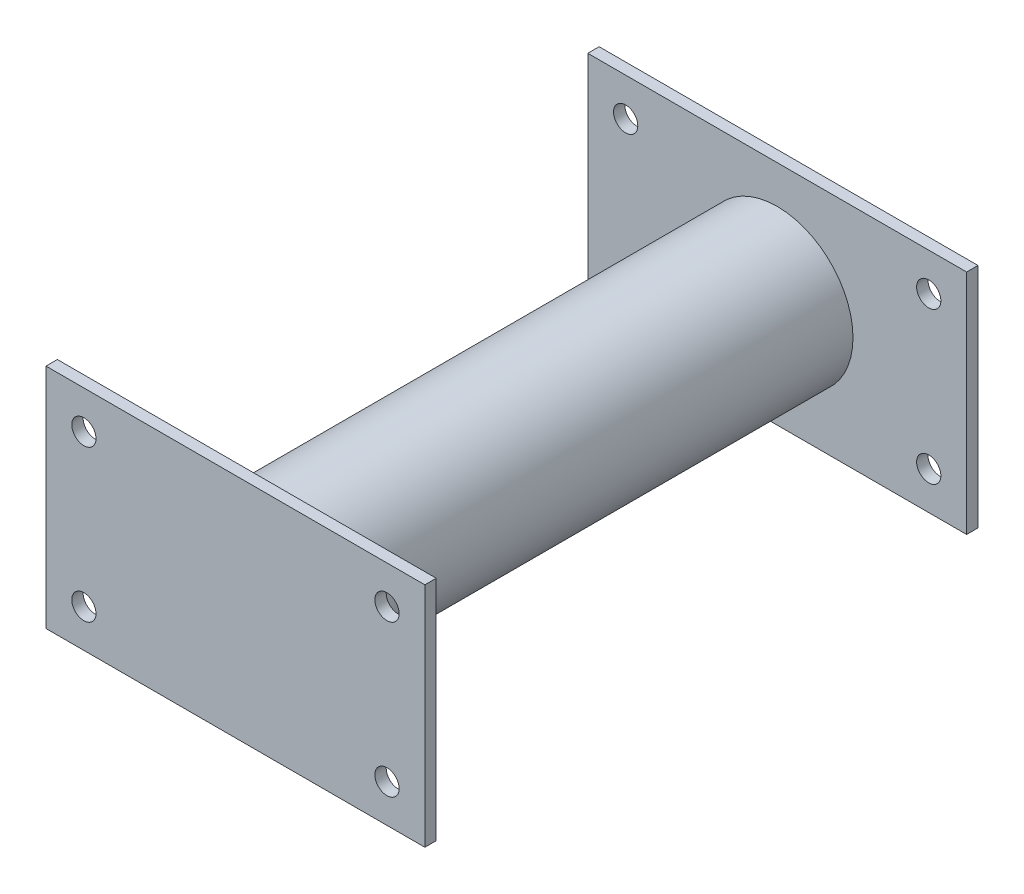
SolidWorks part; units mm, degrees
ref_plane "前基準面" through (0, 0, 0) normal (0, 0, 1) x (1, 0, 0)
ref_plane "上基準面" through (0, 0, 0) normal (0, 1, 0) x (1, 0, 0)
ref_plane "右基準面" through (0, 0, 0) normal (1, 0, 0) x (0, 0, -1)
sketch "草圖1" plane through (0, 0, 0) normal (0, 0, 1) x (1, 0, 0)
  line L1 (-25, 15) -> (25, 15)
  line L2 (-25, 15) -> (-25, -15)
  line L3 (-25, -15) -> (25, -15)
  line L4 (25, 15) -> (25, -15)
  circle A0 centre (-20, 10) radius 1.6
  circle A1 centre (20, 10) radius 1.6
  circle A2 centre (20, -10) radius 1.6
  circle A3 centre (-20, -10) radius 1.6
  dimension "D1" = 5
  dimension "D7" = 3.2
  dimension "D8" = 3.2
  dimension "D9" = 3.2
  dimension "D10" = 3.2
  dimension "D2" = 5
  dimension "D3" = 40
  dimension "D4" = 20
  dimension "D5" = 30
  dimension "D6" = 50
  dimension "D11" = 15
  dimension "D12" = 25
extrude "填料-伸長1" add sketch "草圖1" along normal blind 1.5
sketch "草圖2" plane through (0, 0, 1.5) normal (0, 0, 1) x (1, 0, 0)
  circle A0 centre (0, 0) radius 10
  dimension "D1" = 20
extrude "填料-伸長2" add sketch "草圖2" along normal blind 70
sketch "草圖5" plane through (0, 0, 71.5) normal (0, 0, 1) x (1, 0, 0)
  line L1 (-25, 15) -> (25, 15)
  line L2 (-25, 15) -> (-25, -15)
  line L3 (-25, -15) -> (25, -15)
  line L4 (25, 15) -> (25, -15)
  line L5 (-25, 15) -> (25, -15) construction
  line L6 (-25, -15) -> (25, 15) construction
  circle A0 centre (20, 10) radius 1.6
  circle A1 centre (20, -10) radius 1.6
  circle A3 centre (-20, 10) radius 1.6
  circle A4 centre (-20, -10) radius 1.6
  point P0 (0, 0)
  dimension "D1" = 3.2
  dimension "D2" = 3.2
  dimension "D3" = 3.2
  dimension "D4" = 3.2
extrude "填料-伸長3" add sketch "草圖5" along normal blind 1.5
